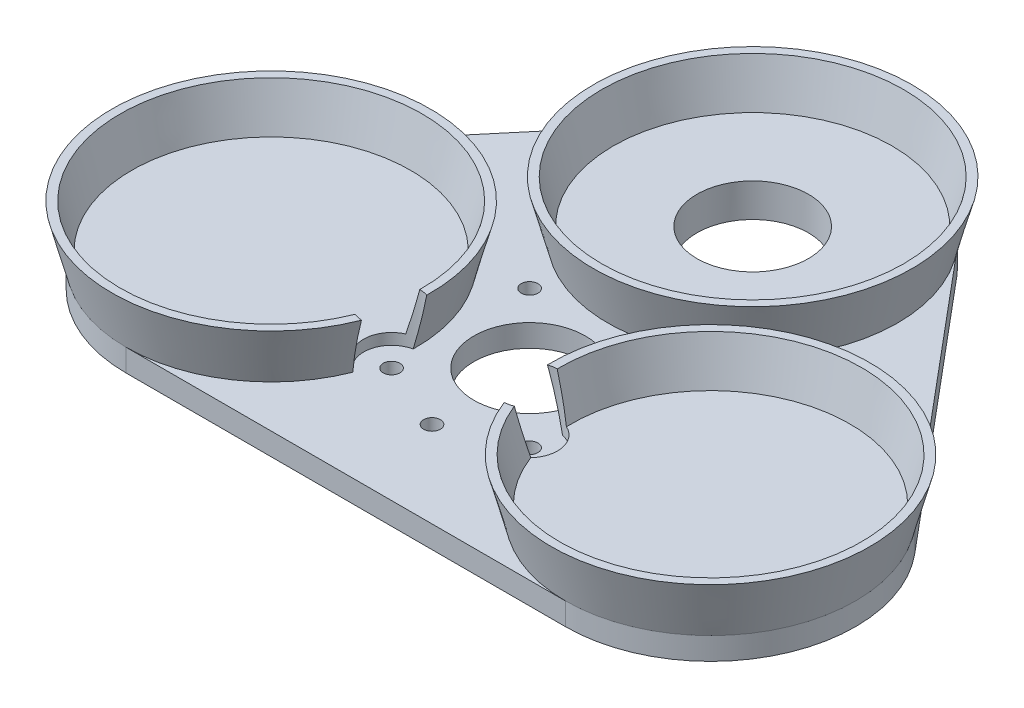
SolidWorks part; units mm, degrees
note: '?' marks a value the reader was unsure of.
material "聚脂树脂"
ref_plane "前视基准面" through (0, 0, 0) normal (0, 0, 1) x (1, 0, 0)
ref_plane "上视基准面" through (0, 0, 0) normal (0, 1, 0) x (1, 0, 0)
ref_plane "右视基准面" through (0, 0, 0) normal (1, 0, 0) x (0, 0, -1)
other "Configuration Table"
sketch "草图1" plane through (0, 0, 0) normal (0, 1, 0) x (1, 0, 0)
  line L0 (0, 0) -> (0, 49.6717) construction
  line L1 (0, 0) -> (68.2454, -12.0335) construction
  line L2 (0, 0) -> (-79.2764, -13.9786) construction
  line L3 (0, 0) -> (75.1475, 0) construction
  line L4 (0, 0) -> (-86.8264, 0) construction
  circle A0 centre (0, 40) radius 26
  circle A1 centre (39.3923, -6.9459) radius 26
  circle A2 centre (-39.3923, -6.9459) radius 26
  dimension "D1" = 52
  dimension "D2" = 52
  dimension "D3" = 52
  dimension "D4" = 40
  dimension "D5" = 40
  dimension "D6" = 40
  dimension "D7" = 10
  dimension "D8" = 10
extrude "凸台-拉伸1" add sketch "草图1" along normal blind 2
sketch "草图2" plane through (0, 0, 0) normal (0, -1, 0) x (1, 0, 0)
  line L0 (-39.3923, 32.9459) -> (39.3923, 32.9459)
  line L1 (0, 0) -> (0, 33.5546) construction
  line L2 (-73.6118, 0) -> (73.6118, 0) construction
  line L3 (-59.3095, -9.7666) -> (-19.9172, -56.7125)
  line L4 (-39.3923, 6.9459) -> (0, -40) construction
  line L5 (0, -40) -> (-29.0608, -64.3849) construction
  line L6 (-29.0608, -64.3849) -> (-68.4531, -17.439) construction
  line L7 (-68.4531, -17.439) -> (-39.3923, 6.9459) construction
  line L8 (59.3095, -9.7666) -> (19.9172, -56.7125)
  circle A0 centre (-39.3923, 6.9459) radius 26 construction
  circle A1 centre (39.3923, 6.9459) radius 26 construction
  circle A2 centre (0, -40) radius 26 construction
  arc A4 (-59.3095, -9.7666) -> (-39.3923, 32.9459) centre (-39.3923, 6.9459) cw
  arc A5 (19.9172, -56.7125) -> (-19.9172, -56.7125) centre (0, -40) cw
  circle A6 centre (0, 0) radius 10
  arc A7 (59.3095, -9.7666) -> (39.3923, 32.9459) centre (39.3923, 6.9459) ccw
  dimension "D1" = 20
extrude "凸台-拉伸2" add sketch "草图2" along normal blind 4
sketch "草图3" plane through (0, 0, 0) normal (0, 1, 0) x (1, 0, 0)
  line L0 (0, 0) -> (33.5505, 33.5505) construction
  line L1 (0, 0) -> (0, 31.7505) construction
  line L2 (0, 0) -> (31.2503, 0) construction
  circle A1 centre (12.3744, 12.3744) radius 1.5
  circle A4 centre (-12.3744, 12.3744) radius 1.5
  circle A5 centre (-12.3744, -12.3744) radius 1.5
  circle A6 centre (12.3744, -12.3744) radius 1.5
  circle A7 centre (0, -17.5) radius 1.5
  dimension "D1" = 3
  dimension "D3" = 3
  dimension "D4" = 17.5
  dimension "D6" = 17.5
  dimension "D5" = 0
  dimension "D2" = 45
extrude "切除-拉伸1" cut sketch "草图3" against normal blind 4
sketch "草图4" plane through (0, 0, 0) normal (1, 0, 0) x (0, 0, -1)
  line L0 (0, 0) -> (0, 27.6583) construction
  line L1 (0, 0) -> (83.286, 0) construction
  line L3 (66, 2) -> (14, 2) construction
  line L5 (68.5706, 9.7274) -> (67.0706, 9.7274)
  line L6 (67.0706, 9.7274) -> (65, 2)
  line L7 (65, 2) -> (40, 2) construction
  line L8 (65, 2) -> (65, 24.8848) construction
  line L9 (40, 2) -> (40, 31.3753) construction
  line L10 (65, 2) -> (66, 2)
  line L11 (66, 2) -> (66, 0)
  line L12 (66, -4) -> (66, 2) construction
  line L13 (66, 0) -> (68.5706, 9.7274)
  dimension "D1" = 8
  dimension "D2" = 25
  dimension "D3" = 15
  dimension "D4" = 1.5
  dimension "D5" = 1
revolve "旋转1" add sketch "草图4" angle 360 about L9
ref_axis "基准轴1" through (0, -6.2571, 0) along (0, 1, 0)?
pattern_circular "阵列(圆周)2" count 2 every 100 about axis through (0, -6.2571, 0) along (0, 1, 0) of "旋转1" other way count 2
sketch "草图5" plane through (0, 0, 0) normal (0, 1, 0) x (1, 0, 0)
  line L2 (0, 0) -> (0, -38.4131) construction
  line L3 (0, -32.9459) -> (61.7369, -32.9459) construction
  line L4 (-39.3923, -32.9459) -> (39.3923, -32.9459) construction
  circle A0 centre (12.3744, -12.3744) radius 5
  circle A1 centre (-12.3744, -12.3744) radius 5
  dimension "D1" = 10
extrude "切除-拉伸2" cut sketch "草图5" along normal blind 10
sketch "草图7" plane through (0, 2, 0) normal (0, 1, 0) x (1, 0, 0)
  circle A0 centre (0, 40) radius 10
  dimension "D1" = 20
extrude "切除-拉伸3" cut sketch "草图7" against normal blind 10
